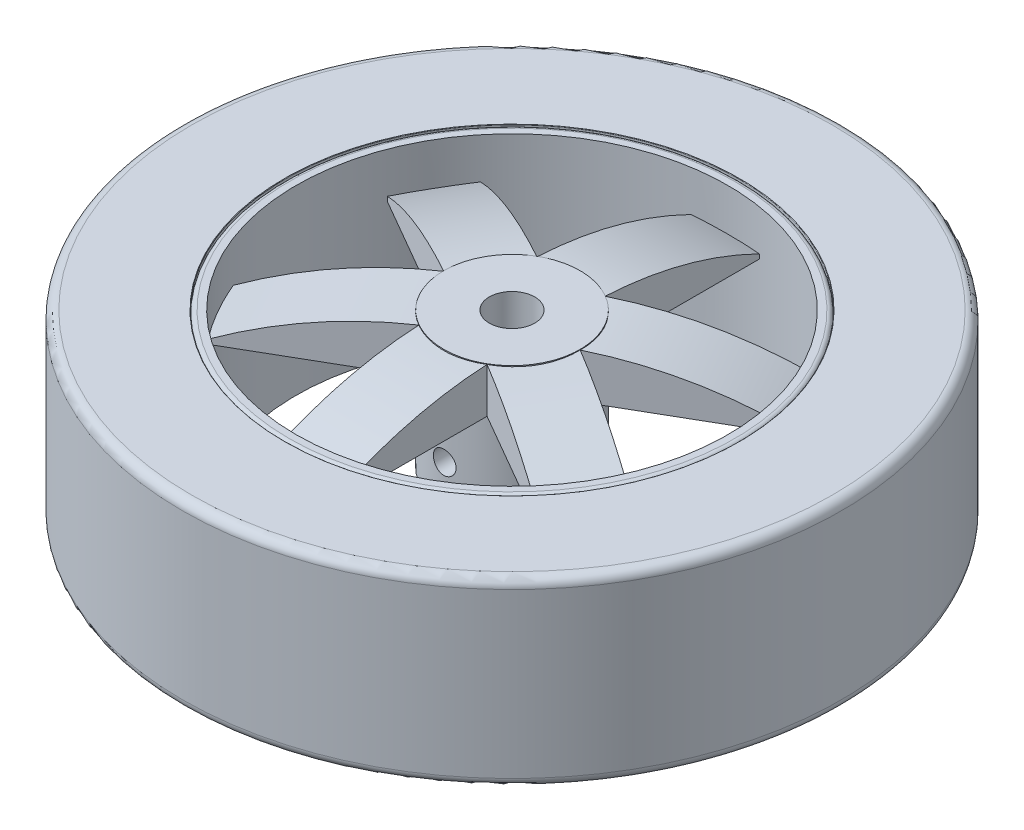
SolidWorks part; units mm, degrees
ref_plane "Front Plane" through (0, 0, 0) normal (0, 0, 1) x (1, 0, 0)
ref_plane "Top Plane" through (0, 0, 0) normal (0, 1, 0) x (1, 0, 0)
ref_plane "Right Plane" through (0, 0, 0) normal (1, 0, 0) x (0, 0, -1)
sketch "Sketch1" plane through (0, 0, 0) normal (0, 1, 0) x (1, 0, 0)
  circle A0 centre (0, 0) radius 50
  circle A1 centre (0, 0) radius 15
  circle A2 centre (0, 0) radius 47.5
  circle A3 centre (0, 0) radius 5
  dimension "D1" = 100
  dimension "D2" = 30
  dimension "D3" = 95
  dimension "D4" = 10
extrude "Boss-Extrude1" add sketch "Sketch1" along normal blind 40 contours A0 A2 | A1 region at (-48.5858, 0, 0) region at (-14.5757, 0, 0)
ref_plane "Plane1" through (0, 20, 0) normal (0, 1, 0) x (1, 0, 0)
sketch "Sketch2" plane through (0, 0, 0) normal (1, 0, 0) x (0, 0, -1)
  line L2 (50, 40) -> (-50, 40) construction
  line L3 (48.8892, 30) -> (8.8892, 30)
  line L4 (8.8892, 30) -> (8.8892, 40)
  spline S0 degree 2 poles (8.8892, 40) (29.8688, 39.8769) (48.8892, 30) knots 0 0 0 1 1 1
  dimension "D1" = 10
  dimension "D2" = 40
  dimension "D5" = 10
extrude "Boss-Extrude2" add sketch "Sketch2" along normal mid plane 15
pattern_circular "CirPattern1" count 6 over 360 about axis through (0, 40, 0) along (0, 1, 0) of "Boss-Extrude2"
fillet "Fillet1" radius 1 2 edges at (0, 0, 50) (0, 40, 50)
sketch "Sketch5" plane through (0, 0, 0) normal (0, 1, 0) x (1, 0, 0)
  circle A0 centre (0, 0) radius 72.5
  circle A1 centre (0, 0) radius 50
  dimension "D1" = 145
  dimension "D2" = 100
extrude "Boss-Extrude4" add sketch "Sketch5" along normal blind 40
fillet "Fillet2" radius 2 2 edges at (0, 0, 72.5) (0, 40, 72.5)
fillet "Fillet3" radius 0.1 1 edges at (0, 40, 50)
sketch "Sketch7" plane through (0, 0, 0) normal (0, -1, 0) x (1, 0, 0)
  circle A1 centre (0, 0) radius 15 construction
  circle A2 centre (0, 0) radius 15
extrude "Cut-Extrude1" cut sketch "Sketch7" against normal blind 10
sketch "Sketch8" plane through (0, 0, 0) normal (0, 0, 1) x (1, 0, 0)
  circle A0 centre (0, 18.5) radius 2.5
  dimension "D1" = 5
  dimension "D2" = 8.5
extrude "Cut-Extrude2" cut sketch "Sketch8" against normal mid plane 35
